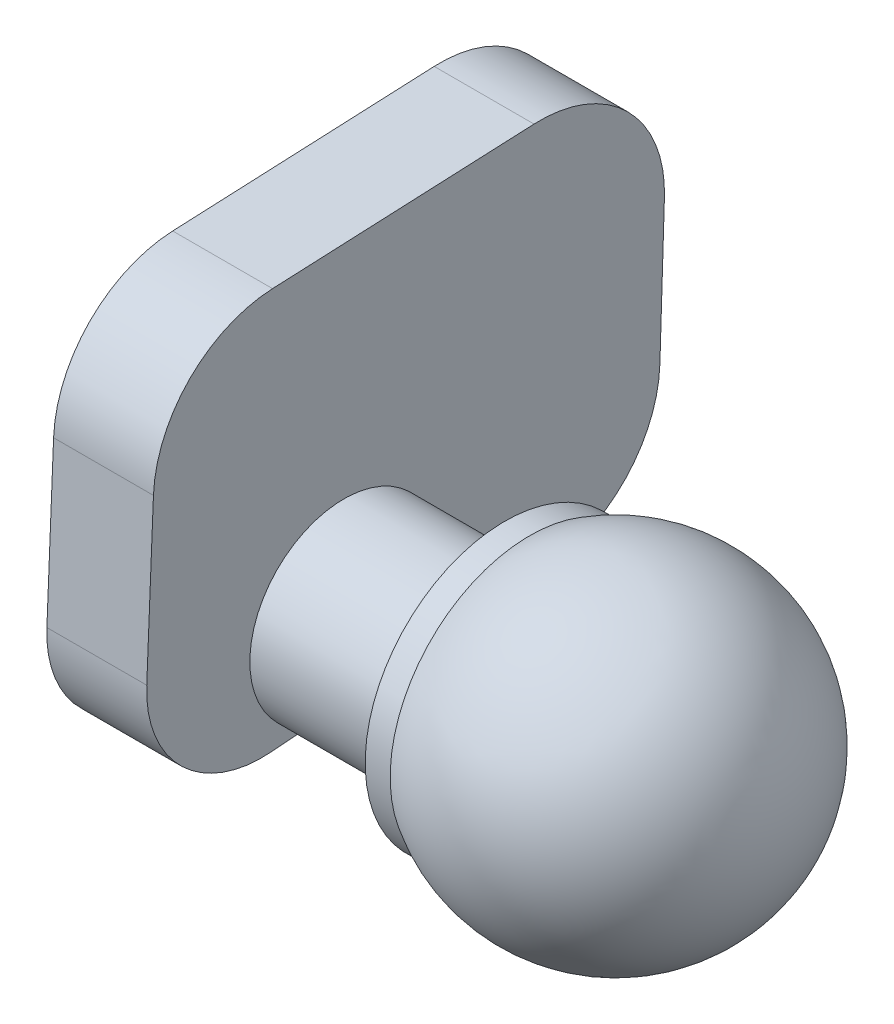
SolidWorks part; units mm, degrees
ref_plane "Front Plane" through (0, 0, 0) normal (0, 0, 1) x (1, 0, 0)
ref_plane "Top Plane" through (0, 0, 0) normal (0, 1, 0) x (1, 0, 0)
ref_plane "Right Plane" through (0, 0, 0) normal (1, 0, 0) x (0, 0, -1)
sketch "Sketch1" plane through (0, 0, 0) normal (1, 0, 0) x (0, 0, -1)
  line L1 (19.6189, 26.9106) -> (30.0933, 27.3824)
  line L2 (14.8482, 22.1234) -> (14.58, 15.6728)
  line L3 (19.5602, 10.8655) -> (30.521, 11.7102)
  line L4 (35.3158, 22.2281) -> (35.1343, 16.536)
  arc A0 (19.5602, 10.8655) -> (14.58, 15.6728) centre (19.2046, 15.4805) cw
  arc A1 (30.0933, 27.3824) -> (35.3158, 22.2281) centre (30.3184, 22.3875) cw
  arc A2 (19.6189, 26.9106) -> (14.8482, 22.1234) centre (19.8439, 21.9156) ccw
  arc A3 (35.1343, 16.536) -> (30.521, 11.7102) centre (30.1368, 16.6954) cw
  point P3 (14.3634, 10.465)
  point P14 (34.9914, 12.0547)
  dimension "D1" = 20.6891
extrude "Boss-Extrude1" add sketch "Sketch1" along normal blind 4
sketch "Sketch2" plane through (4, 0, 0) normal (1, 0, 0) x (0, 0, -1)
  circle A0 centre (22.4785, 14.4187) radius 3.77
extrude "Boss-Extrude3" add sketch "Sketch2" along normal blind 6
sketch "Sketch3" plane through (10, 0, 0) normal (1, 0, 0) x (0, 0, -1)
  circle A0 centre (22.9207, 14.6012) radius 5.5903
extrude "Boss-Extrude4" add sketch "Sketch3" along normal blind 1
dome "Dome2" faces to dome 1 distance 10 reverse direction no elliptical dome no face at (11, 14.6012, -28.511) parameters "D1"=10
